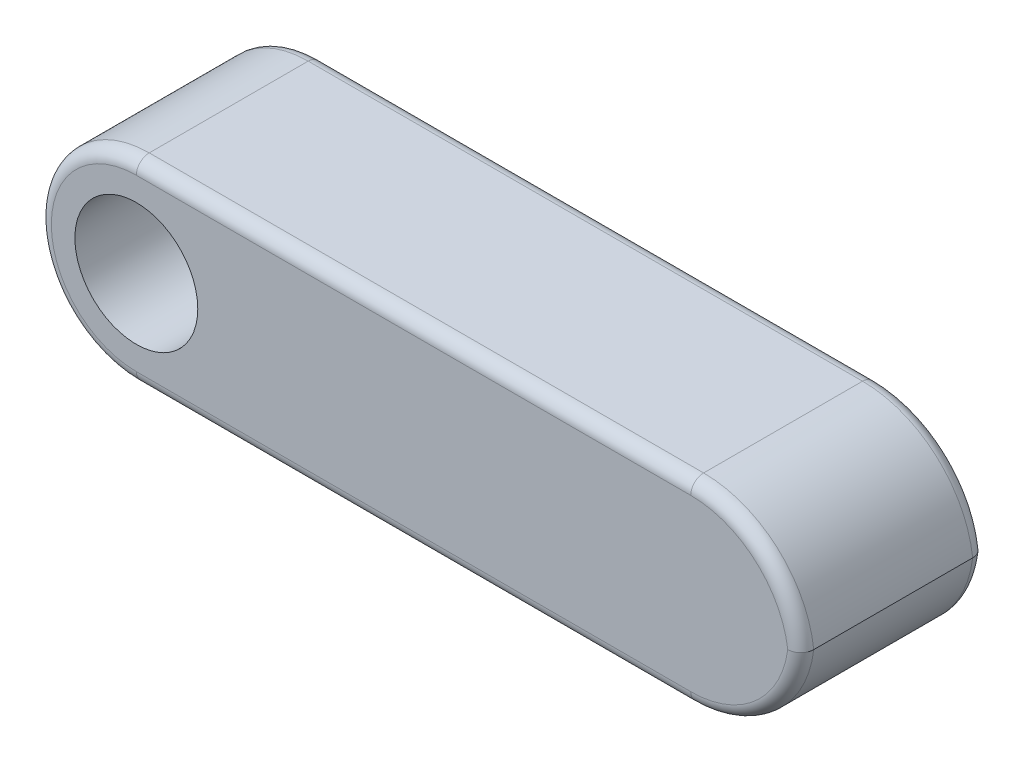
SolidWorks part; units mm, degrees
ref_plane "Front Plane" through (0, 0, 0) normal (0, 0, 1) x (1, 0, 0)
ref_plane "Top Plane" through (0, 0, 0) normal (0, 1, 0) x (1, 0, 0)
ref_plane "Right Plane" through (0, 0, 0) normal (1, 0, 0) x (0, 0, -1)
sketch "Sketch1" plane through (0, 0, 0) normal (0, 0, 1) x (1, 0, 0)
  line L0 (0, 6.731) -> (45.72, 6.731)
  line L1 (0, -6.731) -> (45.72, -6.731)
  line L2 (45.72, 6.731) -> (45.72, -6.731)
  circle A0 centre (0, 0) radius 4.2227
  circle A1 centre (0, 0) radius 6.731
  dimension "D1" = 8.4455
  dimension "D2" = 13.462
  dimension "D3" = 45.72
extrude "Boss-Extrude1" add sketch "Sketch1" along normal blind 12.7 contours A1 L1 L2 L0 | A1 A0 region at (25.4753, 0, 0) region at (4.6249, 4.6249, 0)
fillet "Front Fillet" radius 7.62 2 edges at (45.72, -6.731, 6.35) (45.72, 6.731, 6.35)
fillet "Side Fillet" radius 0.889 10 edges at (19.05, 6.731, 0) (-6.731, 0, 0) (19.05, -6.731, 0) (43.1641, -4.8048, 0) (43.1641, 4.8048, 0) (-6.731, 0, 12.7) (19.05, 6.731, 12.7) (43.1641, 4.8048, 12.7) (43.1641, -4.8048, 12.7) (19.05, -6.731, 12.7)
equation "\"UpperAxleDiameter\"=0.3325"
equation "\"D1@Sketch1\"=\"UpperAxleDiameter\""
equation "\"toeLength\"=1.8"
equation "\"D3@Sketch1\"=\"toeLength\""
equation "\"toeWidth\"= 0.5"
